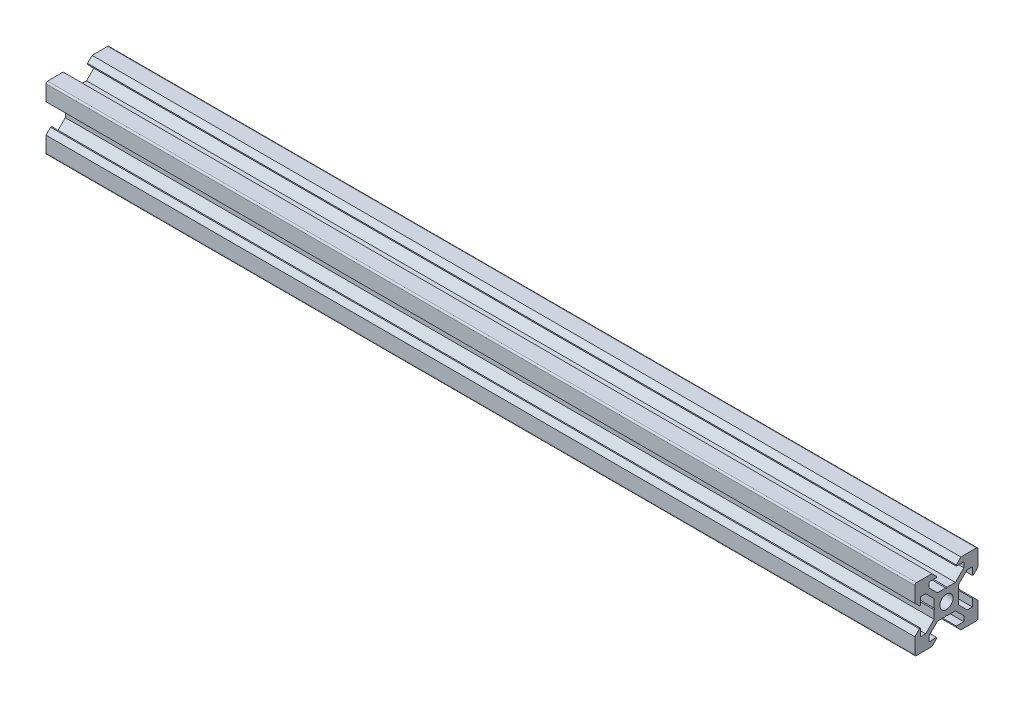
SolidWorks part; units mm, degrees
material "6061-T6 (SS)"
ref_plane "Top" through (0, 0, 0) normal (0, 0, 1) x (1, 0, 0)
ref_plane "Front" through (0, 0, 0) normal (0, 1, 0) x (1, 0, 0)
ref_plane "Right" through (0, 0, 0) normal (1, 0, 0) x (0, 0, -1)
sketch "Profile Sketch" plane through (0, 0, 0) normal (1, 0, 0) x (0, 0, -1)
  line L0 (-0.5, 10) -> (-5.42, 10)
  line L1 (-4.5, 8.2) -> (-4.5, 6.56)
  line L2 (-4.5, 6.56) -> (-7.16, 3.9)
  line L3 (-7.16, 3.9) -> (-9.79, 3.9)
  line L4 (-9.79, 3.9) -> (-10, 3.69)
  line L7 (-3.4387, 5.5) -> (-6.1, 2.8387)
  line L8 (-6.1, 2.8387) -> (-6.1, -0.21)
  line L9 (-6.875, 8.545) -> (-6.875, 8.2)
  line L10 (-6.875, 8.2) -> (-4.5, 8.2)
  line L11 (-6.875, 8.545) -> (-5.42, 10)
  line L12 (0, -10) -> (0, 10) construction
  line L13 (-20, 0) -> (20, 0) construction
  line L14 (-10, -10) -> (-10, 10) construction
  line L15 (-6.875, -8.545) -> (-5.42, -10)
  line L16 (-6.875, -8.2) -> (-4.5, -8.2)
  line L17 (-6.875, -8.545) -> (-6.875, -8.2)
  line L18 (-3.44, -5.5) -> (-6.1, -2.8387)
  line L21 (-7.16, -3.9) -> (-9.79, -3.9)
  line L22 (-4.5, -6.56) -> (-7.16, -3.9)
  line L23 (-4.5, -8.2) -> (-4.5, -6.56)
  line L24 (-0.5, -10) -> (-5.42, -10)
  line L25 (-10, 0) -> (-20, 10) construction
  line L26 (-18.545, 3.125) -> (-18.2, 3.125)
  line L27 (-13.125, -8.545) -> (-13.125, -8.2)
  line L28 (-13.125, -8.2) -> (-15.5, -8.2)
  line L29 (-13.125, -8.545) -> (-14.58, -10)
  line L30 (-15.5, -8.2) -> (-15.5, -6.56)
  line L31 (-15.5, -6.56) -> (-12.84, -3.9)
  line L32 (-12.84, -3.9) -> (-10.21, -3.9)
  line L33 (-20, 4.58) -> (-20, 9.5)
  line L34 (-13.9, 2.8387) -> (-13.9, 0.21)
  line L35 (-16.56, 5.5) -> (-13.9, 2.8387)
  line L36 (-12.84, 3.9) -> (-10.21, 3.9)
  line L37 (-15.5, 6.56) -> (-12.84, 3.9)
  line L38 (-15.5, 8.2) -> (-15.5, 6.56)
  line L39 (-13.125, 8.545) -> (-14.58, 10)
  line L40 (-13.125, 8.2) -> (-15.5, 8.2)
  line L41 (-13.125, 8.545) -> (-13.125, 8.2)
  line L42 (-18.2, 3.125) -> (-18.2, 5.5)
  line L43 (-18.545, 3.125) -> (-20, 4.58)
  line L44 (-18.2, 5.5) -> (-16.56, 5.5)
  line L45 (-14.58, 10) -> (-19.5, 10)
  line L46 (-16.56, -5.5) -> (-13.9, -2.8387)
  line L47 (-14.58, -10) -> (-19.5, -10)
  line L48 (-18.2, -5.5) -> (-16.56, -5.5)
  line L49 (-18.545, -3.125) -> (-20, -4.58)
  line L50 (-18.2, -3.125) -> (-18.2, -5.5)
  line L51 (-20, -4.58) -> (-20, -9.5)
  line L52 (-18.545, -3.125) -> (-18.2, -3.125)
  line L53 (10, -10) -> (10, 10) construction
  line L99 (-10, 3.69) -> (-10.21, 3.9)
  line L100 (-10, -3.69) -> (-10.21, -3.9)
  line L101 (-9.79, -3.9) -> (-10, -3.69)
  line L102 (-13.9, -0.21) -> (-13.69, 0)
  line L103 (-13.69, 0) -> (-13.9, 0.21)
  line L104 (-13.9, -0.21) -> (-13.9, -2.8387)
  line L105 (-6.1, -0.21) -> (-6.31, 0)
  line L106 (-6.31, 0) -> (-6.1, -0.21)
  line L107 (-6.1, -0.21) -> (-6.1, -2.8387)
  line L117 (-5.42, -10) -> (-0.5, -10)
  line L118 (20, -10) -> (20, 10) construction
  line L119 (20, -10) -> (-20, -10) construction
  line L120 (-20, -10) -> (-20, 10) construction
  line L121 (20, 10) -> (-20, 10) construction
  line L122 (20, -10) -> (-20, 10) construction
  line L123 (-20, -10) -> (20, 10) construction
  line L124 (-5.42, 10) -> (-0.5, 10)
  line L125 (-1.455, 3.125) -> (-1.8, 3.125)
  line L126 (-1.455, -3.125) -> (-1.8, -3.125)
  line L127 (-1.8, -5.5) -> (-3.44, -5.5)
  line L128 (-1.8, 5.5) -> (-3.44, 5.5)
  line L129 (-1.8, 3.125) -> (-1.8, 5.5)
  line L130 (-1.8, -3.125) -> (-1.8, -5.5)
  line L131 (0, -4.58) -> (0, -9.5)
  line L132 (0, 4.58) -> (0, 9.5)
  line L133 (-1.455, 3.125) -> (0, 4.58)
  line L134 (-1.455, -3.125) -> (0, -4.58)
  circle A0 centre (-10, 0) radius 2.1
  arc A1 (-19.5, 10) -> (-20, 9.5) centre (-19.5, 9.5) ccw
  arc A2 (-19.5, -10) -> (-20, -9.5) centre (-19.5, -9.5) cw
  arc A3 (-0.5, -10) -> (0, -9.5) centre (-0.5, -9.5) ccw
  arc A4 (-0.5, 10) -> (0, 9.5) centre (-0.5, 9.5) cw
  point P2 (-17.38, 5.5)
  point P35 (-2.4957, 0)
  point P76 (-2.62, 5.5)
  point P108 (0, -8.2)
  point P119 (0, 8.2)
  point P131 (0, 0)
  point P143 (0, 0)
  dimension "D4" = 5.42
  dimension "D5" = 40
  dimension "D6" = 4.2
  dimension "D16" = 0.5
  dimension "D1" = 0.21
  dimension "D2" = 45
  dimension "D3" = 20
  dimension "D7" = 1.5
  dimension "D8" = 1.8
  dimension "D9" = 10
  dimension "D10" = 3.9
  dimension "D11" = 3.9
  dimension "D13" = 3.125
  dimension "D14" = 5.5
  dimension "D15" = 1.64
extrude "Profile Extrude" add sketch "Profile Sketch" along normal blind 275 contours L126 L0 L11 L9 L10 L1 L2 L3 L4 L99 L36 L37 L38 L40 L41 L39 L45 A1 L33 L43 L26 L42 L44 L35 L34 L103 L102 L104 L46 L48 L50 L52 L49 L51 A2 L47 region at (0, 9.6536, 0.3464)
equation "\"M8x1.25_Close_Hole\"= 8.4"
